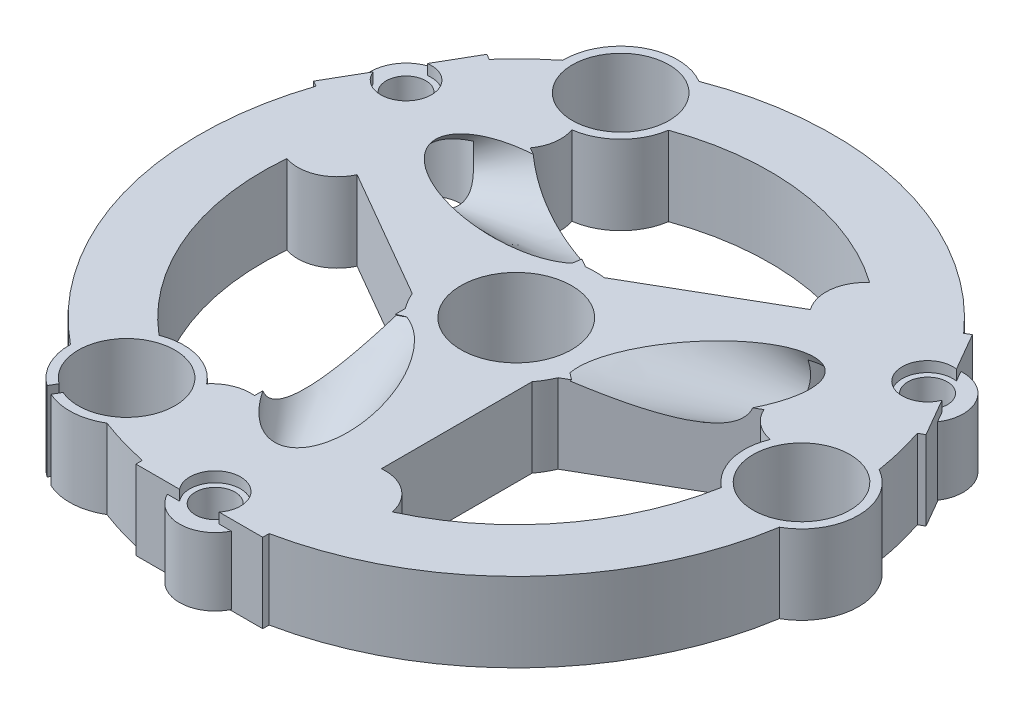
SolidWorks part; units mm, degrees
note: '?' marks a value the reader was unsure of.
other "Moving Tensegrity Frame"
ref_plane "Front Plane" through (0, 0, 0) normal (0, 0, 1) x (1, 0, 0)
ref_plane "Top Plane" through (0, 0, 0) normal (0, 1, 0) x (1, 0, 0)
ref_plane "Right Plane" through (0, 0, 0) normal (1, 0, 0) x (0, 0, -1)
sketch3d "Main Profile Sketch datum points"
  point P0 (0, -96, 0)
  point P1 (10, -96, 0)
  point P2 (0, -96, 10)
ref_plane "Main Profile Sketch plane" through (0, -96, 0) normal (0, -1, 0) x (-1, 0, 0)
sketch "Main Profile Sketch" plane through (0, -96, 0) normal (0, -1, 0) x (-1, 0, 0)
  line L0 (77.2684, -37.7328) -> (76.7153, -36.7748)
  line L1 (77.9277, -36.0748) -> (78.4808, -37.0328)
  line L2 (94.9327, 13.0718) -> (94.2328, 12.6677)
  line L3 (92.1817, 17.8367) -> (94.9327, 13.0718)
  line L4 (86.9327, 26.9282) -> (89.6837, 22.1633)
  line L5 (86.2328, 26.5241) -> (86.9327, 26.9282)
  line L6 (25.6506, 26.9282) -> (26.3505, 26.5241)
  line L7 (22.8996, 22.1633) -> (25.6506, 26.9282)
  line L8 (17.6506, 13.0718) -> (20.4016, 17.8367)
  line L9 (18.3505, 12.6677) -> (17.6506, 13.0718)
  line L10 (48.2917, -40) -> (48.2917, -39.1918)
  line L11 (53.7937, -40) -> (48.2917, -40)
  line L12 (64.2917, -40) -> (58.7897, -40)
  line L13 (64.2917, -39.1918) -> (64.2917, -40)
  line L14 (57.4878, 9.9282) -> (73.964, 19.4407)
  line L15 (38.6193, 19.4407) -> (55.0955, 9.9282)
  line L16 (64.2917, -6) -> (64.2917, -25.0251)
  line L17 (81.964, 5.5843) -> (65.4878, -3.9282)
  line L18 (47.0955, -3.9282) -> (30.6193, 5.5843)
  line L19 (48.2917, -25.0251) -> (48.2917, -6)
  arc A0 (77.9277, -36.0748) -> (76.7153, -36.7748) centre (74.2917, -31.1769) ccw
  arc A1 (78.4808, -37.0328) -> (81.4908, -31.0645) centre (74.2917, -31.1769) ccw
  arc A2 (81.4908, -31.0645) -> (94.2328, 12.6677) centre (56.2917, 0) ccw
  arc A3 (89.6837, 22.1633) -> (92.1817, 17.8367) centre (89.2006, 19) ccw
  arc A4 (86.2328, 26.5241) -> (81.4908, 31.0645) centre (56.2917, 0) ccw
  arc A5 (81.4908, 31.0645) -> (70.5948, 37.3553) centre (74.2917, 31.1769) ccw
  arc A6 (70.5948, 37.3553) -> (26.3505, 26.5241) centre (56.2917, 0) ccw
  arc A7 (20.4016, 17.8367) -> (22.8996, 22.1633) centre (23.3827, 19) ccw
  arc A8 (18.3505, 12.6677) -> (16.7894, 6.2908) centre (56.2917, 0) ccw
  arc A9 (16.7894, 6.2908) -> (16.7894, -6.2908) centre (20.2917, 0) ccw
  arc A10 (16.7894, -6.2908) -> (48.2917, -39.1918) centre (56.2917, 0) ccw
  arc A11 (58.7897, -40) -> (53.7937, -40) centre (56.2917, -38) ccw
  arc A12 (64.2917, -39.1918) -> (70.5948, -37.3553) centre (56.2917, 0) ccw
  arc A13 (70.5948, -37.3553) -> (77.2684, -37.7328) centre (74.2917, -31.1769) ccw
  circle A14 centre (74.2917, 31.1769) radius 6.1
  arc A15 (38.6193, 19.4407) -> (37.8344, 26.1406) centre (34.5609, 22.3612) ccw
  arc A16 (67.1737, 30.0929) -> (37.8344, 26.1406) centre (56.2917, 0) ccw
  arc A17 (67.1737, 30.0929) -> (73.314, 24.0436) centre (74.2917, 31.1769) ccw
  arc A18 (73.314, 24.0436) -> (73.964, 19.4407) centre (78.0224, 22.3612) ccw
  arc A19 (57.4878, 9.9282) -> (55.0955, 9.9282) centre (56.2917, 0) ccw
  arc A20 (68.6029, -26.7636) -> (64.2917, -25.0251) centre (64.7917, -30) ccw
  arc A21 (64.2917, -6) -> (65.4878, -3.9282) centre (56.2917, 0) ccw
  arc A22 (81.964, 5.5843) -> (88.1587, 2.9141) centre (86.5224, 7.6388) ccw
  arc A23 (76.9118, -24.4706) -> (88.1587, 2.9141) centre (56.2917, 0) ccw
  arc A24 (76.9118, -24.4706) -> (68.6029, -26.7636) centre (74.2917, -31.1769) ccw
  circle A25 centre (20.2917, 0) radius 6.1
  arc A26 (48.2917, -25.0251) -> (42.8818, -29.0547) centre (47.7917, -30) ccw
  arc A27 (24.7894, -5.6223) -> (42.8818, -29.0547) centre (56.2917, 0) ccw
  arc A28 (24.7894, -5.6223) -> (26.9581, 2.7199) centre (20.2917, 0) ccw
  arc A29 (26.9581, 2.7199) -> (30.6193, 5.5843) centre (26.0609, 7.6388) ccw
  arc A30 (47.0955, -3.9282) -> (48.2917, -6) centre (56.2917, 0) ccw
extrude "Main Extrusion" add sketch "Main Profile Sketch" along normal blind 1 separate body
sketch3d "Detail Profile 2 Sketch datum points"
  point P0 (0, -97, 0)
  point P1 (10, -97, 0)
  point P2 (0, -97, 10)
ref_plane "Detail Profile 2 Sketch plane" through (0, -97, 0) normal (0, -1, 0) x (-1, 0, 0)
sketch "Detail Profile 2 Sketch" plane through (0, -97, 0) normal (0, -1, 0) x (-1, 0, 0)
  line L0 (77.2684, -37.7328) -> (76.7153, -36.7748)
  line L1 (77.9277, -36.0748) -> (78.4808, -37.0328)
  line L2 (94.9327, 13.0718) -> (94.2328, 12.6677)
  line L3 (92.1817, 17.8367) -> (94.9327, 13.0718)
  line L4 (86.9327, 26.9282) -> (89.6837, 22.1633)
  line L5 (86.2328, 26.5241) -> (86.9327, 26.9282)
  line L6 (25.6506, 26.9282) -> (26.3505, 26.5241)
  line L7 (22.8996, 22.1633) -> (25.6506, 26.9282)
  line L8 (17.6506, 13.0718) -> (20.4016, 17.8367)
  line L9 (18.3505, 12.6677) -> (17.6506, 13.0718)
  line L10 (48.2917, -40) -> (48.2917, -39.1918)
  line L11 (53.7937, -40) -> (48.2917, -40)
  line L12 (64.2917, -40) -> (58.7897, -40)
  line L13 (64.2917, -39.1918) -> (64.2917, -40)
  line L14 (79.1224, 17.3833) -> (79.1224, 12.6167)
  line L15 (57.4878, 9.9282) -> (73.964, 19.4407)
  line L16 (38.6193, 19.4407) -> (55.0955, 9.9282)
  line L17 (64.2917, -6) -> (64.2917, -25.0251)
  line L18 (81.964, 5.5843) -> (65.4878, -3.9282)
  line L19 (59.9306, -28.4637) -> (55.8027, -26.0804)
  line L20 (29.8219, 11.0804) -> (33.9499, 13.4637)
  line L21 (47.0955, -3.9282) -> (30.6193, 5.5843)
  line L22 (48.2917, -25.0251) -> (48.2917, -6)
  arc A0 (77.9277, -36.0748) -> (76.7153, -36.7748) centre (74.2917, -31.1769) ccw
  arc A1 (78.4808, -37.0328) -> (81.4908, -31.0645) centre (74.2917, -31.1769) ccw
  arc A2 (81.4908, -31.0645) -> (94.2328, 12.6677) centre (56.2917, 0) ccw
  arc A3 (89.6837, 22.1633) -> (92.1817, 17.8367) centre (89.2006, 19) ccw
  arc A4 (86.2328, 26.5241) -> (81.4908, 31.0645) centre (56.2917, 0) ccw
  arc A5 (81.4908, 31.0645) -> (70.5948, 37.3553) centre (74.2917, 31.1769) ccw
  arc A6 (70.5948, 37.3553) -> (26.3505, 26.5241) centre (56.2917, 0) ccw
  arc A7 (20.4016, 17.8367) -> (22.8996, 22.1633) centre (23.3827, 19) ccw
  arc A8 (18.3505, 12.6677) -> (16.7894, 6.2908) centre (56.2917, 0) ccw
  arc A9 (16.7894, 6.2908) -> (16.7894, -6.2908) centre (20.2917, 0) ccw
  arc A10 (16.7894, -6.2908) -> (48.2917, -39.1918) centre (56.2917, 0) ccw
  arc A11 (58.7897, -40) -> (53.7937, -40) centre (56.2917, -38) ccw
  arc A12 (64.2917, -39.1918) -> (70.5948, -37.3553) centre (56.2917, 0) ccw
  arc A13 (70.5948, -37.3553) -> (77.2684, -37.7328) centre (74.2917, -31.1769) ccw
  arc A14 (79.1224, 12.6167) -> (79.1224, 17.3833) centre (82.2724, 15) ccw
  circle A15 centre (74.2917, 31.1769) radius 6.1
  arc A16 (38.6193, 19.4407) -> (37.8344, 26.1406) centre (34.5609, 22.3612) ccw
  arc A17 (67.1737, 30.0929) -> (37.8344, 26.1406) centre (56.2917, 0) ccw
  arc A18 (67.1737, 30.0929) -> (73.314, 24.0436) centre (74.2917, 31.1769) ccw
  arc A19 (73.314, 24.0436) -> (73.964, 19.4407) centre (78.0224, 22.3612) ccw
  arc A20 (57.4878, 9.9282) -> (55.0955, 9.9282) centre (56.2917, 0) ccw
  arc A21 (68.6029, -26.7636) -> (64.2917, -25.0251) centre (64.7917, -30) ccw
  arc A22 (64.2917, -6) -> (65.4878, -3.9282) centre (56.2917, 0) ccw
  arc A23 (81.964, 5.5843) -> (88.1587, 2.9141) centre (86.5224, 7.6388) ccw
  arc A24 (76.9118, -24.4706) -> (88.1587, 2.9141) centre (56.2917, 0) ccw
  arc A25 (76.9118, -24.4706) -> (68.6029, -26.7636) centre (74.2917, -31.1769) ccw
  arc A26 (55.8027, -26.0804) -> (52.3417, -30) centre (56.2917, -30) ccw
  arc A27 (52.3417, -30) -> (59.9306, -28.4637) centre (56.2917, -30) ccw
  arc A28 (33.9499, 13.4637) -> (26.3609, 15) centre (30.3109, 15) ccw
  arc A29 (26.3609, 15) -> (29.8219, 11.0804) centre (30.3109, 15) ccw
  circle A30 centre (20.2917, 0) radius 6.1
  arc A31 (48.2917, -25.0251) -> (42.8818, -29.0547) centre (47.7917, -30) ccw
  arc A32 (24.7894, -5.6223) -> (42.8818, -29.0547) centre (56.2917, 0) ccw
  arc A33 (24.7894, -5.6223) -> (26.9581, 2.7199) centre (20.2917, 0) ccw
  arc A34 (26.9581, 2.7199) -> (30.6193, 5.5843) centre (26.0609, 7.6388) ccw
  arc A35 (47.0955, -3.9282) -> (48.2917, -6) centre (56.2917, 0) ccw
extrude "Detail Extrusion 2" add sketch "Detail Profile 2 Sketch" along normal blind 0.31
sketch3d "Detail Profile 3 Sketch datum points"
  point P0 (0, -97.31, 0)
  point P1 (10, -97.31, 0)
  point P2 (0, -97.31, 10)
ref_plane "Detail Profile 3 Sketch plane" through (0, -97.31, 0) normal (0, -1, 0) x (-1, 0, 0)
sketch "Detail Profile 3 Sketch" plane through (0, -97.31, 0) normal (0, -1, 0) x (-1, 0, 0)
  line L0 (77.2684, -37.7328) -> (76.7153, -36.7748)
  line L1 (77.9277, -36.0748) -> (78.4808, -37.0328)
  line L2 (94.9327, 13.0718) -> (94.2328, 12.6677)
  line L3 (92.9482, 16.5089) -> (94.9327, 13.0718)
  line L4 (86.9327, 26.9282) -> (88.9171, 23.4911)
  line L5 (86.2328, 26.5241) -> (86.9327, 26.9282)
  line L6 (25.6506, 26.9282) -> (26.3505, 26.5241)
  line L7 (23.6662, 23.4911) -> (25.6506, 26.9282)
  line L8 (17.6506, 13.0718) -> (19.6351, 16.5089)
  line L9 (18.3505, 12.6677) -> (17.6506, 13.0718)
  line L10 (48.2917, -40) -> (48.2917, -39.1918)
  line L11 (52.2605, -40) -> (48.2917, -40)
  line L12 (64.2917, -40) -> (60.3228, -40)
  line L13 (64.2917, -39.1918) -> (64.2917, -40)
  line L14 (79.1224, 17.3833) -> (79.1224, 12.6167)
  line L15 (57.4878, 9.9282) -> (73.964, 19.4407)
  line L16 (38.6193, 19.4407) -> (55.0955, 9.9282)
  line L17 (64.2917, -6) -> (64.2917, -25.0251)
  line L18 (81.964, 5.5843) -> (65.4878, -3.9282)
  line L19 (59.9306, -28.4637) -> (55.8027, -26.0804)
  line L20 (29.8219, 11.0804) -> (33.9499, 13.4637)
  line L21 (47.0955, -3.9282) -> (30.6193, 5.5843)
  line L22 (48.2917, -25.0251) -> (48.2917, -6)
  arc A0 (77.9277, -36.0748) -> (76.7153, -36.7748) centre (74.2917, -31.1769) ccw
  arc A1 (78.4808, -37.0328) -> (81.4908, -31.0645) centre (74.2917, -31.1769) ccw
  arc A2 (81.4908, -31.0645) -> (94.2328, 12.6677) centre (56.2917, 0) ccw
  arc A3 (92.9482, 16.5089) -> (88.9171, 23.4911) centre (89.2006, 19) ccw
  arc A4 (86.2328, 26.5241) -> (81.4908, 31.0645) centre (56.2917, 0) ccw
  arc A5 (81.4908, 31.0645) -> (70.5948, 37.3553) centre (74.2917, 31.1769) ccw
  arc A6 (70.5948, 37.3553) -> (26.3505, 26.5241) centre (56.2917, 0) ccw
  arc A7 (23.6662, 23.4911) -> (19.6351, 16.5089) centre (23.3827, 19) ccw
  arc A8 (18.3505, 12.6677) -> (16.7894, 6.2908) centre (56.2917, 0) ccw
  arc A9 (16.7894, 6.2908) -> (16.7894, -6.2908) centre (20.2917, 0) ccw
  arc A10 (16.7894, -6.2908) -> (48.2917, -39.1918) centre (56.2917, 0) ccw
  arc A11 (52.2605, -40) -> (60.3228, -40) centre (56.2917, -38) ccw
  arc A12 (64.2917, -39.1918) -> (70.5948, -37.3553) centre (56.2917, 0) ccw
  arc A13 (70.5948, -37.3553) -> (77.2684, -37.7328) centre (74.2917, -31.1769) ccw
  circle A14 centre (89.2006, 19) radius 2.5
  arc A15 (79.1224, 12.6167) -> (79.1224, 17.3833) centre (82.2724, 15) ccw
  circle A16 centre (74.2917, 31.1769) radius 6.1
  arc A17 (38.6193, 19.4407) -> (37.8344, 26.1406) centre (34.5609, 22.3612) ccw
  arc A18 (67.1737, 30.0929) -> (37.8344, 26.1406) centre (56.2917, 0) ccw
  arc A19 (67.1737, 30.0929) -> (73.314, 24.0436) centre (74.2917, 31.1769) ccw
  arc A20 (73.314, 24.0436) -> (73.964, 19.4407) centre (78.0224, 22.3612) ccw
  arc A21 (57.4878, 9.9282) -> (55.0955, 9.9282) centre (56.2917, 0) ccw
  arc A22 (68.6029, -26.7636) -> (64.2917, -25.0251) centre (64.7917, -30) ccw
  arc A23 (64.2917, -6) -> (65.4878, -3.9282) centre (56.2917, 0) ccw
  arc A24 (81.964, 5.5843) -> (88.1587, 2.9141) centre (86.5224, 7.6388) ccw
  arc A25 (76.9118, -24.4706) -> (88.1587, 2.9141) centre (56.2917, 0) ccw
  arc A26 (76.9118, -24.4706) -> (68.6029, -26.7636) centre (74.2917, -31.1769) ccw
  arc A27 (55.8027, -26.0804) -> (52.3417, -30) centre (56.2917, -30) ccw
  arc A28 (52.3417, -30) -> (59.9306, -28.4637) centre (56.2917, -30) ccw
  circle A29 centre (56.2917, -38) radius 2.5
  arc A30 (33.9499, 13.4637) -> (26.3609, 15) centre (30.3109, 15) ccw
  arc A31 (26.3609, 15) -> (29.8219, 11.0804) centre (30.3109, 15) ccw
  circle A32 centre (23.3827, 19) radius 2.5
  circle A33 centre (20.2917, 0) radius 6.1
  arc A34 (48.2917, -25.0251) -> (42.8818, -29.0547) centre (47.7917, -30) ccw
  arc A35 (24.7894, -5.6223) -> (42.8818, -29.0547) centre (56.2917, 0) ccw
  arc A36 (24.7894, -5.6223) -> (26.9581, 2.7199) centre (20.2917, 0) ccw
  arc A37 (26.9581, 2.7199) -> (30.6193, 5.5843) centre (26.0609, 7.6388) ccw
  arc A38 (47.0955, -3.9282) -> (48.2917, -6) centre (56.2917, 0) ccw
extrude "Detail Extrusion 3" add sketch "Detail Profile 3 Sketch" along normal blind 0.4
sketch3d "Detail Profile 4 Sketch datum points"
  point P0 (0, -97.71, 0)
  point P1 (10, -97.71, 0)
  point P2 (0, -97.71, 10)
ref_plane "Detail Profile 4 Sketch plane" through (0, -97.71, 0) normal (0, -1, 0) x (-1, 0, 0)
sketch "Detail Profile 4 Sketch" plane through (0, -97.71, 0) normal (0, -1, 0) x (-1, 0, 0)
  line L0 (77.2684, -37.7328) -> (76.7153, -36.7748)
  line L1 (77.9277, -36.0748) -> (78.4808, -37.0328)
  line L2 (94.9327, 13.0718) -> (94.2328, 12.6677)
  line L3 (92.9482, 16.5089) -> (94.9327, 13.0718)
  line L4 (86.9327, 26.9282) -> (88.9171, 23.4911)
  line L5 (86.2328, 26.5241) -> (86.9327, 26.9282)
  line L6 (25.6506, 26.9282) -> (26.3505, 26.5241)
  line L7 (23.6662, 23.4911) -> (25.6506, 26.9282)
  line L8 (17.6506, 13.0718) -> (19.6351, 16.5089)
  line L9 (18.3505, 12.6677) -> (17.6506, 13.0718)
  line L10 (48.2917, -40) -> (48.2917, -39.1918)
  line L11 (52.2605, -40) -> (48.2917, -40)
  line L12 (64.2917, -40) -> (60.3228, -40)
  line L13 (64.2917, -39.1918) -> (64.2917, -40)
  line L14 (57.4878, 9.9282) -> (73.964, 19.4407)
  line L15 (38.6193, 19.4407) -> (55.0955, 9.9282)
  line L16 (64.2917, -6) -> (64.2917, -25.0251)
  line L17 (81.964, 5.5843) -> (65.4878, -3.9282)
  line L18 (47.0955, -3.9282) -> (30.6193, 5.5843)
  line L19 (48.2917, -25.0251) -> (48.2917, -6)
  arc A0 (77.9277, -36.0748) -> (76.7153, -36.7748) centre (74.2917, -31.1769) ccw
  arc A1 (78.4808, -37.0328) -> (81.4908, -31.0645) centre (74.2917, -31.1769) ccw
  arc A2 (81.4908, -31.0645) -> (94.2328, 12.6677) centre (56.2917, 0) ccw
  arc A3 (92.9482, 16.5089) -> (88.9171, 23.4911) centre (89.2006, 19) ccw
  arc A4 (86.2328, 26.5241) -> (81.4908, 31.0645) centre (56.2917, 0) ccw
  arc A5 (81.4908, 31.0645) -> (70.5948, 37.3553) centre (74.2917, 31.1769) ccw
  arc A6 (70.5948, 37.3553) -> (26.3505, 26.5241) centre (56.2917, 0) ccw
  arc A7 (23.6662, 23.4911) -> (19.6351, 16.5089) centre (23.3827, 19) ccw
  arc A8 (18.3505, 12.6677) -> (16.7894, 6.2908) centre (56.2917, 0) ccw
  arc A9 (16.7894, 6.2908) -> (16.7894, -6.2908) centre (20.2917, 0) ccw
  arc A10 (16.7894, -6.2908) -> (48.2917, -39.1918) centre (56.2917, 0) ccw
  arc A11 (52.2605, -40) -> (60.3228, -40) centre (56.2917, -38) ccw
  arc A12 (64.2917, -39.1918) -> (70.5948, -37.3553) centre (56.2917, 0) ccw
  arc A13 (70.5948, -37.3553) -> (77.2684, -37.7328) centre (74.2917, -31.1769) ccw
  circle A14 centre (89.2006, 19) radius 2.5
  circle A15 centre (82.2724, 15) radius 3.95
  circle A16 centre (74.2917, 31.1769) radius 6.1
  arc A17 (38.6193, 19.4407) -> (37.8344, 26.1406) centre (34.5609, 22.3612) ccw
  arc A18 (67.1737, 30.0929) -> (37.8344, 26.1406) centre (56.2917, 0) ccw
  arc A19 (67.1737, 30.0929) -> (73.314, 24.0436) centre (74.2917, 31.1769) ccw
  arc A20 (73.314, 24.0436) -> (73.964, 19.4407) centre (78.0224, 22.3612) ccw
  arc A21 (57.4878, 9.9282) -> (55.0955, 9.9282) centre (56.2917, 0) ccw
  arc A22 (68.6029, -26.7636) -> (64.2917, -25.0251) centre (64.7917, -30) ccw
  arc A23 (64.2917, -6) -> (65.4878, -3.9282) centre (56.2917, 0) ccw
  arc A24 (81.964, 5.5843) -> (88.1587, 2.9141) centre (86.5224, 7.6388) ccw
  arc A25 (76.9118, -24.4706) -> (88.1587, 2.9141) centre (56.2917, 0) ccw
  arc A26 (76.9118, -24.4706) -> (68.6029, -26.7636) centre (74.2917, -31.1769) ccw
  circle A27 centre (56.2917, -30) radius 3.95
  circle A28 centre (56.2917, -38) radius 2.5
  circle A29 centre (30.3109, 15) radius 3.95
  circle A30 centre (23.3827, 19) radius 2.5
  circle A31 centre (20.2917, 0) radius 6.1
  arc A32 (48.2917, -25.0251) -> (42.8818, -29.0547) centre (47.7917, -30) ccw
  arc A33 (24.7894, -5.6223) -> (42.8818, -29.0547) centre (56.2917, 0) ccw
  arc A34 (24.7894, -5.6223) -> (26.9581, 2.7199) centre (20.2917, 0) ccw
  arc A35 (26.9581, 2.7199) -> (30.6193, 5.5843) centre (26.0609, 7.6388) ccw
  arc A36 (47.0955, -3.9282) -> (48.2917, -6) centre (56.2917, 0) ccw
extrude "Detail Extrusion 4" add sketch "Detail Profile 4 Sketch" along normal blind 2.99
sketch3d "Detail Profile 5 Sketch datum points"
  point P0 (0, -100.7, 0)
  point P1 (10, -100.7, 0)
  point P2 (0, -100.7, 10)
ref_plane "Detail Profile 5 Sketch plane" through (0, -100.7, 0) normal (0, -1, 0) x (-1, 0, 0)
sketch "Detail Profile 5 Sketch" plane through (0, -100.7, 0) normal (0, -1, 0) x (-1, 0, 0)
  line L0 (77.2684, -37.7328) -> (76.7153, -36.7748)
  line L1 (77.9277, -36.0748) -> (78.4808, -37.0328)
  line L2 (94.9327, 13.0718) -> (94.2328, 12.6677)
  line L3 (92.9482, 16.5089) -> (94.9327, 13.0718)
  line L4 (86.9327, 26.9282) -> (88.9171, 23.4911)
  line L5 (86.2328, 26.5241) -> (86.9327, 26.9282)
  line L6 (25.6506, 26.9282) -> (26.3505, 26.5241)
  line L7 (23.6662, 23.4911) -> (25.6506, 26.9282)
  line L8 (17.6506, 13.0718) -> (19.6351, 16.5089)
  line L9 (18.3505, 12.6677) -> (17.6506, 13.0718)
  line L10 (48.2917, -40) -> (48.2917, -39.1918)
  line L11 (52.2605, -40) -> (48.2917, -40)
  line L12 (64.2917, -40) -> (60.3228, -40)
  line L13 (64.2917, -39.1918) -> (64.2917, -40)
  line L14 (57.4878, 9.9282) -> (73.964, 19.4407)
  line L15 (38.6193, 19.4407) -> (55.0955, 9.9282)
  line L16 (64.2917, -6) -> (64.2917, -25.0251)
  line L17 (81.964, 5.5843) -> (65.4878, -3.9282)
  line L18 (47.0955, -3.9282) -> (30.6193, 5.5843)
  line L19 (48.2917, -25.0251) -> (48.2917, -6)
  arc A0 (77.9277, -36.0748) -> (76.7153, -36.7748) centre (74.2917, -31.1769) ccw
  arc A1 (78.4808, -37.0328) -> (81.4908, -31.0645) centre (74.2917, -31.1769) ccw
  arc A2 (81.4908, -31.0645) -> (94.2328, 12.6677) centre (56.2917, 0) ccw
  arc A3 (92.9482, 16.5089) -> (88.9171, 23.4911) centre (89.2006, 19) ccw
  arc A4 (86.2328, 26.5241) -> (81.4908, 31.0645) centre (56.2917, 0) ccw
  arc A5 (81.4908, 31.0645) -> (70.5948, 37.3553) centre (74.2917, 31.1769) ccw
  arc A6 (70.5948, 37.3553) -> (26.3505, 26.5241) centre (56.2917, 0) ccw
  arc A7 (23.6662, 23.4911) -> (19.6351, 16.5089) centre (23.3827, 19) ccw
  arc A8 (18.3505, 12.6677) -> (16.7894, 6.2908) centre (56.2917, 0) ccw
  arc A9 (16.7894, 6.2908) -> (16.7894, -6.2908) centre (20.2917, 0) ccw
  arc A10 (16.7894, -6.2908) -> (48.2917, -39.1918) centre (56.2917, 0) ccw
  arc A11 (52.2605, -40) -> (60.3228, -40) centre (56.2917, -38) ccw
  arc A12 (64.2917, -39.1918) -> (70.5948, -37.3553) centre (56.2917, 0) ccw
  arc A13 (70.5948, -37.3553) -> (77.2684, -37.7328) centre (74.2917, -31.1769) ccw
  circle A14 centre (78.0224, 22.3612) radius 1.1
  circle A15 centre (89.2006, 19) radius 2.5
  circle A16 centre (86.5224, 7.6388) radius 1.1
  circle A17 centre (82.2724, 15) radius 3.95
  circle A18 centre (74.2917, 31.1769) radius 6.1
  arc A19 (38.6193, 19.4407) -> (37.8344, 26.1406) centre (34.5609, 22.3612) ccw
  arc A20 (67.1737, 30.0929) -> (37.8344, 26.1406) centre (56.2917, 0) ccw
  arc A21 (67.1737, 30.0929) -> (73.314, 24.0436) centre (74.2917, 31.1769) ccw
  arc A22 (73.314, 24.0436) -> (73.964, 19.4407) centre (78.0224, 22.3612) ccw
  arc A23 (57.4878, 9.9282) -> (55.0955, 9.9282) centre (56.2917, 0) ccw
  arc A24 (68.6029, -26.7636) -> (64.2917, -25.0251) centre (64.7917, -30) ccw
  arc A25 (64.2917, -6) -> (65.4878, -3.9282) centre (56.2917, 0) ccw
  arc A26 (81.964, 5.5843) -> (88.1587, 2.9141) centre (86.5224, 7.6388) ccw
  arc A27 (76.9118, -24.4706) -> (88.1587, 2.9141) centre (56.2917, 0) ccw
  arc A28 (76.9118, -24.4706) -> (68.6029, -26.7636) centre (74.2917, -31.1769) ccw
  circle A29 centre (64.7917, -30) radius 1.1
  circle A30 centre (56.2917, -30) radius 3.95
  circle A31 centre (56.2917, -38) radius 2.5
  circle A32 centre (34.5609, 22.3612) radius 1.1
  circle A33 centre (30.3109, 15) radius 3.95
  circle A34 centre (26.0609, 7.6388) radius 1.1
  circle A35 centre (23.3827, 19) radius 2.5
  circle A36 centre (20.2917, 0) radius 6.1
  arc A37 (48.2917, -25.0251) -> (42.8818, -29.0547) centre (47.7917, -30) ccw
  arc A38 (24.7894, -5.6223) -> (42.8818, -29.0547) centre (56.2917, 0) ccw
  arc A39 (24.7894, -5.6223) -> (26.9581, 2.7199) centre (20.2917, 0) ccw
  arc A40 (26.9581, 2.7199) -> (30.6193, 5.5843) centre (26.0609, 7.6388) ccw
  arc A41 (47.0955, -3.9282) -> (48.2917, -6) centre (56.2917, 0) ccw
  circle A42 centre (47.7917, -30) radius 1.1
extrude "Detail Extrusion 5" add sketch "Detail Profile 5 Sketch" along normal blind 1.3
sketch3d "Detail Profile 6 Sketch datum points"
  point P0 (0, -102, 0)
  point P1 (10, -102, 0)
  point P2 (0, -102, 10)
ref_plane "Detail Profile 6 Sketch plane" through (0, -102, 0) normal (0, -1, 0) x (-1, 0, 0)
sketch "Detail Profile 6 Sketch" plane through (0, -102, 0) normal (0, -1, 0) x (-1, 0, 0)
  line L0 (77.2684, -37.7328) -> (76.7153, -36.7748)
  line L1 (77.9277, -36.0748) -> (78.4808, -37.0328)
  line L2 (94.9327, 13.0718) -> (94.2328, 12.6677)
  line L3 (92.9482, 16.5089) -> (94.9327, 13.0718)
  line L4 (86.9327, 26.9282) -> (88.9171, 23.4911)
  line L5 (86.2328, 26.5241) -> (86.9327, 26.9282)
  line L6 (25.6506, 26.9282) -> (26.3505, 26.5241)
  line L7 (23.6662, 23.4911) -> (25.6506, 26.9282)
  line L8 (17.6506, 13.0718) -> (19.6351, 16.5089)
  line L9 (18.3505, 12.6677) -> (17.6506, 13.0718)
  line L10 (48.2917, -40) -> (48.2917, -39.1918)
  line L11 (52.2605, -40) -> (48.2917, -40)
  line L12 (64.2917, -40) -> (60.3228, -40)
  line L13 (64.2917, -39.1918) -> (64.2917, -40)
  line L14 (57.4878, 9.9282) -> (73.964, 19.4407)
  line L15 (38.6193, 19.4407) -> (55.0955, 9.9282)
  line L16 (64.2917, -6) -> (64.2917, -25.0251)
  line L17 (81.964, 5.5843) -> (65.4878, -3.9282)
  line L18 (47.0955, -3.9282) -> (30.6193, 5.5843)
  line L19 (48.2917, -25.0251) -> (48.2917, -6)
  arc A0 (77.9277, -36.0748) -> (76.7153, -36.7748) centre (74.2917, -31.1769) ccw
  arc A1 (78.4808, -37.0328) -> (81.4908, -31.0645) centre (74.2917, -31.1769) ccw
  arc A2 (81.4908, -31.0645) -> (94.2328, 12.6677) centre (56.2917, 0) ccw
  arc A3 (92.9482, 16.5089) -> (88.9171, 23.4911) centre (89.2006, 19) ccw
  arc A4 (86.2328, 26.5241) -> (81.4908, 31.0645) centre (56.2917, 0) ccw
  arc A5 (81.4908, 31.0645) -> (70.5948, 37.3553) centre (74.2917, 31.1769) ccw
  arc A6 (70.5948, 37.3553) -> (26.3505, 26.5241) centre (56.2917, 0) ccw
  arc A7 (23.6662, 23.4911) -> (19.6351, 16.5089) centre (23.3827, 19) ccw
  arc A8 (18.3505, 12.6677) -> (16.7894, 6.2908) centre (56.2917, 0) ccw
  arc A9 (16.7894, 6.2908) -> (16.7894, -6.2908) centre (20.2917, 0) ccw
  arc A10 (16.7894, -6.2908) -> (48.2917, -39.1918) centre (56.2917, 0) ccw
  arc A11 (52.2605, -40) -> (60.3228, -40) centre (56.2917, -38) ccw
  arc A12 (64.2917, -39.1918) -> (70.5948, -37.3553) centre (56.2917, 0) ccw
  arc A13 (70.5948, -37.3553) -> (77.2684, -37.7328) centre (74.2917, -31.1769) ccw
  circle A14 centre (78.0224, 22.3612) radius 1.75
  circle A15 centre (89.2006, 19) radius 2.5
  circle A16 centre (86.5224, 7.6388) radius 1.75
  circle A17 centre (82.2724, 15) radius 3.95
  circle A18 centre (74.2917, 31.1769) radius 6.1
  arc A19 (38.6193, 19.4407) -> (37.8344, 26.1406) centre (34.5609, 22.3612) ccw
  arc A20 (67.1737, 30.0929) -> (37.8344, 26.1406) centre (56.2917, 0) ccw
  arc A21 (67.1737, 30.0929) -> (73.314, 24.0436) centre (74.2917, 31.1769) ccw
  arc A22 (73.314, 24.0436) -> (73.964, 19.4407) centre (78.0224, 22.3612) ccw
  arc A23 (57.4878, 9.9282) -> (55.0955, 9.9282) centre (56.2917, 0) ccw
  arc A24 (68.6029, -26.7636) -> (64.2917, -25.0251) centre (64.7917, -30) ccw
  arc A25 (64.2917, -6) -> (65.4878, -3.9282) centre (56.2917, 0) ccw
  arc A26 (81.964, 5.5843) -> (88.1587, 2.9141) centre (86.5224, 7.6388) ccw
  arc A27 (76.9118, -24.4706) -> (88.1587, 2.9141) centre (56.2917, 0) ccw
  arc A28 (76.9118, -24.4706) -> (68.6029, -26.7636) centre (74.2917, -31.1769) ccw
  circle A29 centre (64.7917, -30) radius 1.75
  circle A30 centre (56.2917, -30) radius 3.95
  circle A31 centre (56.2917, -38) radius 2.5
  circle A32 centre (34.5609, 22.3612) radius 1.75
  circle A33 centre (30.3109, 15) radius 3.95
  circle A34 centre (26.0609, 7.6388) radius 1.75
  circle A35 centre (23.3827, 19) radius 2.5
  circle A36 centre (20.2917, 0) radius 6.1
  arc A37 (48.2917, -25.0251) -> (42.8818, -29.0547) centre (47.7917, -30) ccw
  arc A38 (24.7894, -5.6223) -> (42.8818, -29.0547) centre (56.2917, 0) ccw
  arc A39 (24.7894, -5.6223) -> (26.9581, 2.7199) centre (20.2917, 0) ccw
  arc A40 (26.9581, 2.7199) -> (30.6193, 5.5843) centre (26.0609, 7.6388) ccw
  arc A41 (47.0955, -3.9282) -> (48.2917, -6) centre (56.2917, 0) ccw
  circle A42 centre (47.7917, -30) radius 1.75
extrude "Detail Extrusion 6" add sketch "Detail Profile 6 Sketch" along normal blind 3.89
sketch3d "Detail Profile 7 Sketch datum points"
  point P0 (0, -105.89, 0)
  point P1 (10, -105.89, 0)
  point P2 (0, -105.89, 10)
ref_plane "Detail Profile 7 Sketch plane" through (0, -105.89, 0) normal (0, -1, 0) x (-1, 0, 0)
sketch "Detail Profile 7 Sketch" plane through (0, -105.89, 0) normal (0, -1, 0) x (-1, 0, 0)
  line L0 (77.2684, -37.7328) -> (76.7153, -36.7748)
  line L1 (77.9277, -36.0748) -> (78.4808, -37.0328)
  line L2 (94.9327, 13.0718) -> (94.2328, 12.6677)
  line L3 (91.6827, 18.701) -> (94.9327, 13.0718)
  line L4 (86.9327, 26.9282) -> (90.1827, 21.299)
  line L5 (86.2328, 26.5241) -> (86.9327, 26.9282)
  line L6 (25.6506, 26.9282) -> (26.3505, 26.5241)
  line L7 (22.4006, 21.299) -> (25.6506, 26.9282)
  line L8 (17.6506, 13.0718) -> (20.9006, 18.701)
  line L9 (18.3505, 12.6677) -> (17.6506, 13.0718)
  line L10 (48.2917, -40) -> (48.2917, -39.1918)
  line L11 (54.7917, -40) -> (48.2917, -40)
  line L12 (64.2917, -40) -> (57.7917, -40)
  line L13 (64.2917, -39.1918) -> (64.2917, -40)
  line L14 (57.4878, 9.9282) -> (73.964, 19.4407)
  line L15 (38.6193, 19.4407) -> (55.0955, 9.9282)
  line L16 (64.2917, -6) -> (64.2917, -25.0251)
  line L17 (81.964, 5.5843) -> (65.4878, -3.9282)
  line L18 (47.0955, -3.9282) -> (30.6193, 5.5843)
  line L19 (48.2917, -25.0251) -> (48.2917, -6)
  arc A0 (77.9277, -36.0748) -> (76.7153, -36.7748) centre (74.2917, -31.1769) ccw
  arc A1 (78.4808, -37.0328) -> (81.4908, -31.0645) centre (74.2917, -31.1769) ccw
  arc A2 (81.4908, -31.0645) -> (94.2328, 12.6677) centre (56.2917, 0) ccw
  arc A3 (89.2006, 21.5) -> (91.6827, 18.701) centre (89.2006, 19) ccw
  arc A4 (90.1827, 21.299) -> (89.2006, 21.5) centre (89.2006, 19) ccw
  arc A5 (86.2328, 26.5241) -> (81.4908, 31.0645) centre (56.2917, 0) ccw
  arc A6 (81.4908, 31.0645) -> (70.5948, 37.3553) centre (74.2917, 31.1769) ccw
  arc A7 (70.5948, 37.3553) -> (26.3505, 26.5241) centre (56.2917, 0) ccw
  arc A8 (23.3827, 21.5) -> (22.4006, 21.299) centre (23.3827, 19) ccw
  arc A9 (20.9006, 18.701) -> (23.3827, 21.5) centre (23.3827, 19) ccw
  arc A10 (18.3505, 12.6677) -> (16.7894, 6.2908) centre (56.2917, 0) ccw
  arc A11 (16.7894, 6.2908) -> (16.7894, -6.2908) centre (20.2917, 0) ccw
  arc A12 (16.7894, -6.2908) -> (48.2917, -39.1918) centre (56.2917, 0) ccw
  arc A13 (56.2917, -35.5) -> (54.7917, -40) centre (56.2917, -38) ccw
  arc A14 (57.7917, -40) -> (56.2917, -35.5) centre (56.2917, -38) ccw
  arc A15 (64.2917, -39.1918) -> (70.5948, -37.3553) centre (56.2917, 0) ccw
  arc A16 (70.5948, -37.3553) -> (77.2684, -37.7328) centre (74.2917, -31.1769) ccw
  circle A17 centre (78.0224, 22.3612) radius 1.75
  circle A18 centre (86.5224, 7.6388) radius 1.75
  circle A19 centre (82.2724, 15) radius 3.95
  circle A20 centre (74.2917, 31.1769) radius 6.1
  arc A21 (38.6193, 19.4407) -> (37.8344, 26.1406) centre (34.5609, 22.3612) ccw
  arc A22 (67.1737, 30.0929) -> (37.8344, 26.1406) centre (56.2917, 0) ccw
  arc A23 (67.1737, 30.0929) -> (73.314, 24.0436) centre (74.2917, 31.1769) ccw
  arc A24 (73.314, 24.0436) -> (73.964, 19.4407) centre (78.0224, 22.3612) ccw
  arc A25 (57.4878, 9.9282) -> (55.0955, 9.9282) centre (56.2917, 0) ccw
  arc A26 (68.6029, -26.7636) -> (64.2917, -25.0251) centre (64.7917, -30) ccw
  arc A27 (64.2917, -6) -> (65.4878, -3.9282) centre (56.2917, 0) ccw
  arc A28 (81.964, 5.5843) -> (88.1587, 2.9141) centre (86.5224, 7.6388) ccw
  arc A29 (76.9118, -24.4706) -> (88.1587, 2.9141) centre (56.2917, 0) ccw
  arc A30 (76.9118, -24.4706) -> (68.6029, -26.7636) centre (74.2917, -31.1769) ccw
  circle A31 centre (64.7917, -30) radius 1.75
  circle A32 centre (56.2917, -30) radius 3.95
  circle A33 centre (34.5609, 22.3612) radius 1.75
  circle A34 centre (30.3109, 15) radius 3.95
  circle A35 centre (26.0609, 7.6388) radius 1.75
  arc A36 (48.2917, -25.0251) -> (42.8818, -29.0547) centre (47.7917, -30) ccw
  arc A37 (24.7894, -5.6223) -> (42.8818, -29.0547) centre (56.2917, 0) ccw
  arc A38 (24.7894, -5.6223) -> (26.9581, 2.7199) centre (20.2917, 0) ccw
  arc A39 (26.9581, 2.7199) -> (30.6193, 5.5843) centre (26.0609, 7.6388) ccw
  arc A40 (47.0955, -3.9282) -> (48.2917, -6) centre (56.2917, 0) ccw
  circle A41 centre (47.7917, -30) radius 1.75
  circle A42 centre (20.2917, 0) radius 6.1
extrude "Detail Extrusion 7" add sketch "Detail Profile 7 Sketch" along normal blind 0.11
sketch3d "Compression Articulation Throat 61 axis line"
  line L0 (-90.6158, -106.3831, -16.1872) -> (-73.929, -95.6169, -13.8128) construction
ref_axis "Compression Articulation Throat 61 axis" through (-90.6158, -106.3831, -16.1872) along (0.8343, 0.5383, 0.1187)?
sketch3d "Compression Articulation Throat 61 Sketch datum points"
  point P0 (-82.2724, -101, -15)
  point P1 (-82.2724, -98.8462, -24.7653)
  point P2 (-73.929, -95.6169, -13.8128)
ref_plane "Compression Articulation Throat 61 Sketch plane" through (21.8481, -32.2924, -7.1221) normal (0.5512, -0.8148, -0.1797) x (-0.8343, -0.5383, -0.1187)
sketch "Compression Articulation Throat 61 Sketch" plane through (21.8481, -32.2924, -7.1221) normal (0.5512, -0.8148, -0.1797) x (-0.8343, -0.5383, -0.1187)
  line L0 (124.7935, -7.105) -> (124.7935, -4.805)
  line L1 (124.7935, -4.805) -> (101.7935, 1.915)
  line L2 (101.7935, 1.915) -> (101.7935, -7.105)
  line L3 (101.7935, -7.105) -> (124.7935, -7.105)
revolve "Compression Articulation Throat 61" cut sketch "Compression Articulation Throat 61 Sketch" angle 360 about axis through (-90.6158, -106.3831, -16.1872) along (0.8343, 0.5383, 0.1187)
sketch3d "Compression Articulation Throat 68 axis line"
  line L0 (-25.111, -106.3831, -21.632) -> (-35.5108, -95.6169, -8.368) construction
ref_axis "Compression Articulation Throat 68 axis" through (-25.111, -106.3831, -21.632) along (-0.52, 0.5383, 0.6632)?
sketch3d "Compression Articulation Throat 68 Sketch datum points"
  point P0 (-30.3109, -101, -15)
  point P1 (-30.3109, -93.2358, -21.3021)
  point P2 (-35.5108, -95.6169, -8.368)
ref_plane "Compression Articulation Throat 68 Sketch plane" through (-55.5594, -21.3154, -26.2607) normal (0.8542, 0.3277, 0.4037) x (0.3769, 0.1446, -0.9149)
sketch "Compression Articulation Throat 68 Sketch" plane through (-55.5594, -21.3154, -26.2607) normal (0.8542, 0.3277, 0.4037) x (0.3769, 0.1446, -0.9149)
  line L0 (-12.3085, -83.4412) -> (-10.7241, -81.7739)
  line L1 (-10.7241, -81.7739) -> (-22.7679, -61.059)
  line L2 (-22.7679, -61.059) -> (-28.9813, -67.5977)
  line L3 (-28.9813, -67.5977) -> (-12.3085, -83.4412)
revolve "Compression Articulation Throat 68" cut sketch "Compression Articulation Throat 68 Sketch" angle 360 about axis through (-25.111, -106.3831, -21.632) along (-0.52, 0.5383, 0.6632)
sketch3d "Compression Articulation Throat 75 axis line"
  line L0 (-53.1481, -106.3831, 37.8192) -> (-59.4352, -95.6169, 22.1808) construction
ref_axis "Compression Articulation Throat 75 axis" through (-53.1481, -106.3831, 37.8192) along (-0.3144, 0.5383, -0.7819)?
sketch3d "Compression Articulation Throat 75 Sketch datum points"
  point P0 (-56.2917, -101, 30)
  point P1 (-56.2917, -109.2368, 24.3295)
  point P2 (-59.4352, -95.6169, 22.1808)
ref_plane "Compression Articulation Throat 75 Sketch plane" through (-75.1941, -14.1195, 20.5094) normal (0.9493, 0.1783, -0.2589) x (-0.2545, -0.0478, -0.9659)
sketch "Compression Articulation Throat 75 Sketch" plane through (-75.1941, -14.1195, 20.5094) normal (0.9493, 0.1783, -0.2589) x (-0.2545, -0.0478, -0.9659)
  line L0 (-9.8257, -88.8766) -> (-8.4754, -90.7385)
  line L1 (-8.4754, -90.7385) -> (14.089, -82.6758)
  line L2 (14.089, -82.6758) -> (8.7936, -75.3739)
  line L3 (8.7936, -75.3739) -> (-9.8257, -88.8766)
revolve "Compression Articulation Throat 75" cut sketch "Compression Articulation Throat 75 Sketch" angle 360 about axis through (-53.1481, -106.3831, 37.8192) along (-0.3144, 0.5383, -0.7819)
sketch3d "Centre Inspection Opening Sketch datum points"
  point P0 (0, -110, 0)
  point P1 (10, -110, 0)
  point P2 (0, -110, -10)
ref_plane "Centre Inspection Opening Sketch plane" through (0, -110, 0) normal (0, 1, 0) x (1, 0, 0)
sketch "Centre Inspection Opening Sketch" plane through (0, -110, 0) normal (0, 1, 0) x (1, 0, 0)
  circle A0 centre (-56.2917, 0) radius 7
extrude "Centre Inspection Opening" cut sketch "Centre Inspection Opening Sketch" along normal blind 30
